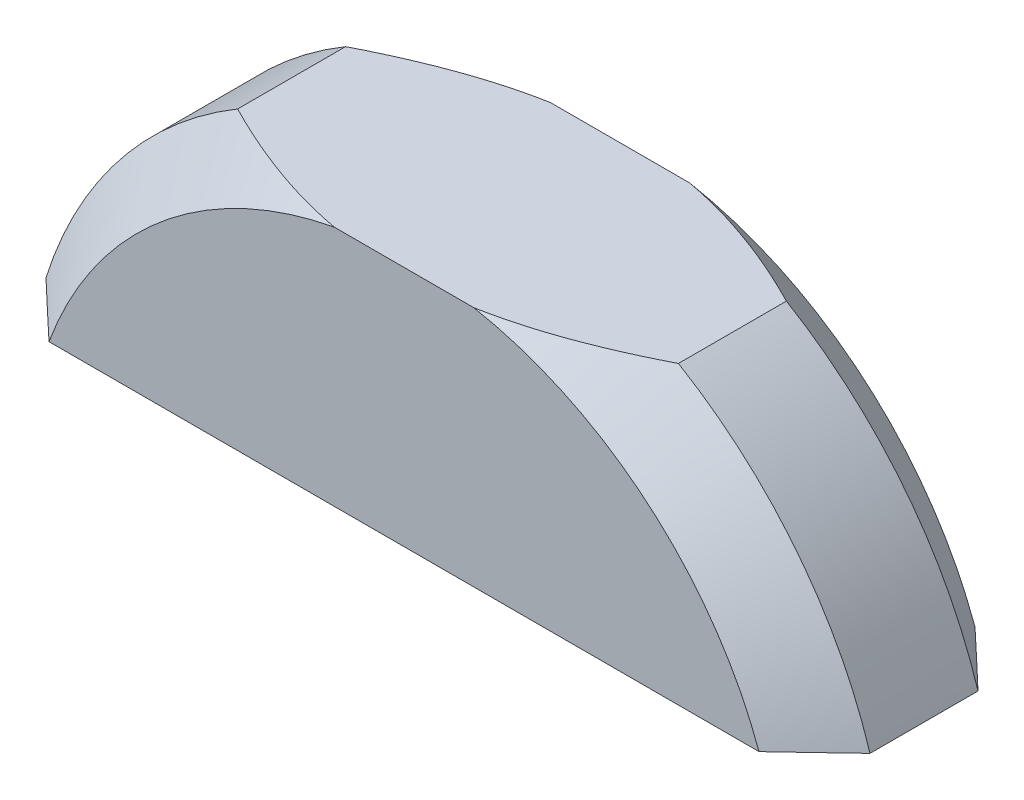
SolidWorks part; units mm, degrees
ref_plane "front" through (0, 0, 0) normal (0, 0, 1) x (1, 0, 0)
ref_plane "top" through (0, 0, 0) normal (0, 1, 0) x (1, 0, 0)
ref_plane "right" through (0, 0, 0) normal (1, 0, 0) x (0, 0, -1)
sketch "body" plane through (0, 0, 0) normal (0, 0, 1) x (1, 0, 0)
  line L0 (-1.9079, 0.6) -> (1.9079, 0.6)
  line L1 (-1.0206, 1.72) -> (1.0206, 1.72)
  arc A0 (-1.9079, 0.6) -> (-1.0206, 1.72) centre (0, 0) cw
  arc A1 (1.0206, 1.72) -> (1.9079, 0.6) centre (0, 0) cw
extrude "Extrude1" add sketch "body" along normal blind 1
chamfer "Chamfer1" distance 0.25 4 edges at (-1.5677, 1.2419, 0) (1.5677, 1.2419, 0) (1.5677, 1.2419, 1) (-1.5677, 1.2419, 1)
equation "\"Height2@body\" = \"Height@body\" * 4 / 5"
